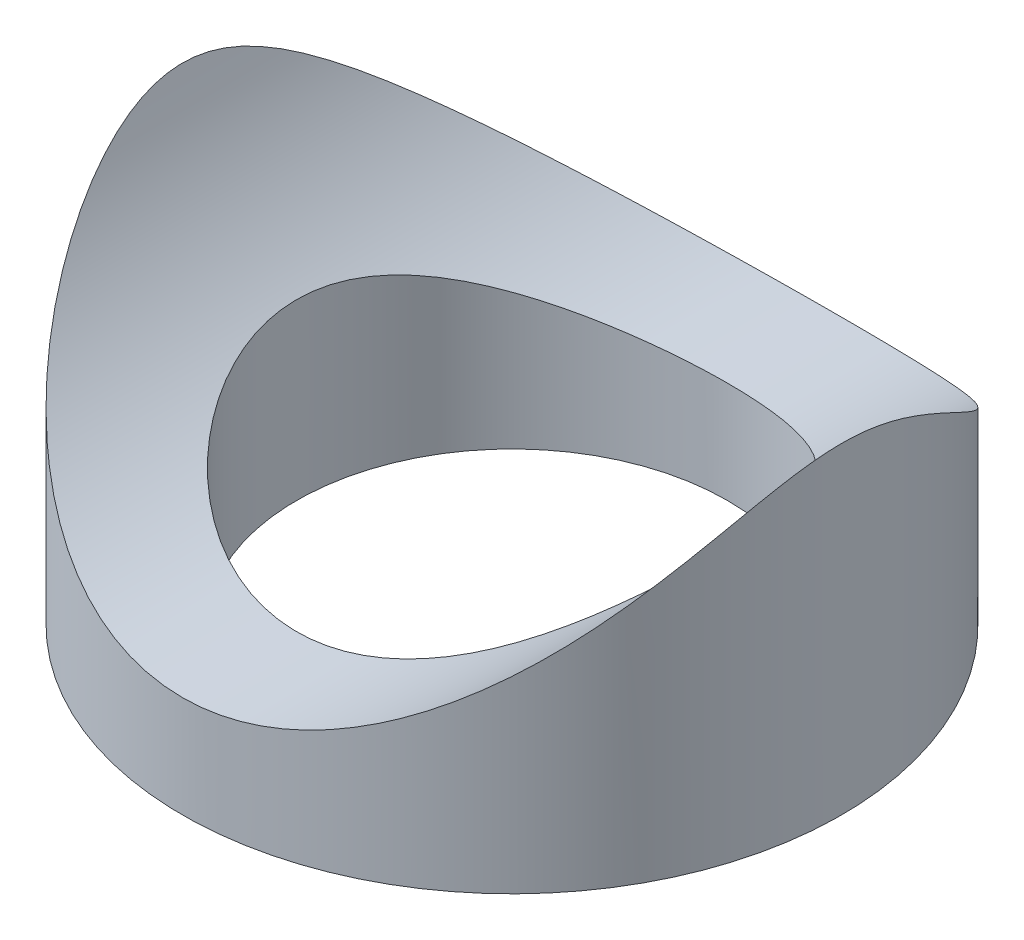
SolidWorks part; units mm, degrees
material "PTFE (general)"
ref_plane "Front Plane" through (0, 0, 0) normal (0, 0, 1) x (1, 0, 0)
ref_plane "Top Plane" through (0, 0, 0) normal (0, 1, 0) x (1, 0, 0)
ref_plane "Right Plane" through (0, 0, 0) normal (1, 0, 0) x (0, 0, -1)
sketch "Sketch1" plane through (0, 0, 0) normal (0, 1, 0) x (1, 0, 0)
  circle A0 centre (0, 0) radius 7.65
  circle A1 centre (0, 0) radius 5
  dimension "D1" = 10
  dimension "D2" = 15.3
extrude "Boss-Extrude1" add sketch "Sketch1" along normal blind 10
sketch "Sketch2" plane through (0, 0, 0) normal (0, 0, 1) x (1, 0, 0)
  line L0 (0, -5.5) -> (0, 5.5) construction
  circle A0 centre (0, 9.64) radius 8.28
  dimension "D2" = 16.56
  dimension "D3" = 9.64
  dimension "D1" = 0
extrude "Cut-Extrude1" cut sketch "Sketch2" against normal through all both and the other way through all
sketch "Sketch3" plane through (0, 0, 0) normal (0, -1, 0) x (1, 0, 0)
  circle A0 centre (0, 0) radius 7.65
  circle A1 centre (0, 0) radius 5
  circle A2 centre (0, 0) radius 7.65 construction
  dimension "D1" = 0
extrude "Boss-Extrude2" add sketch "Sketch3" along normal blind 1
